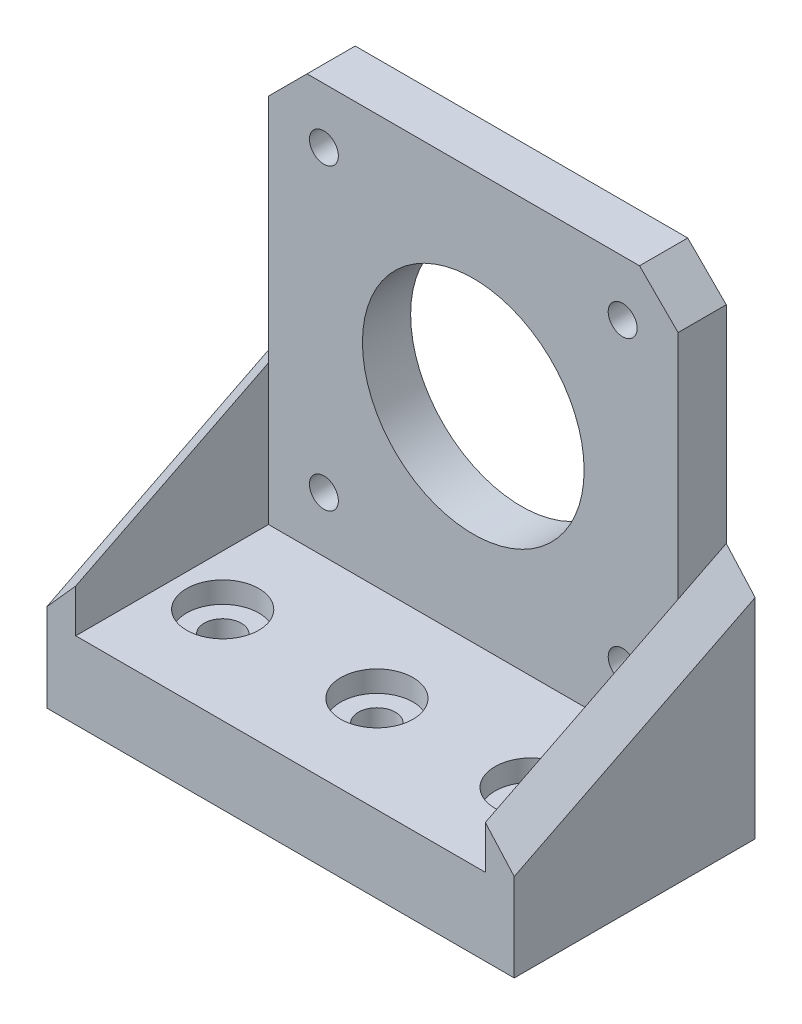
SolidWorks part; units mm, degrees
ref_plane "Front Plane" through (0, 0, 0) normal (0, 0, 1) x (1, 0, 0)
ref_plane "Top Plane" through (0, 0, 0) normal (0, 1, 0) x (1, 0, 0)
ref_plane "Right Plane" through (0, 0, 0) normal (1, 0, 0) x (0, 0, -1)
sketch "Sketch1" plane through (0, 0, 0) normal (0, 0, 1) x (1, 0, 0)
  line L0 (0, 0) -> (0, 10.5968) construction
  line L1 (-21.25, -21.25) -> (21.25, -21.25)
  line L2 (-21.25, -21.25) -> (-21.25, 21.25)
  line L3 (-21.25, 21.25) -> (21.25, 21.25)
  line L4 (21.25, -21.25) -> (21.25, 21.25)
  line L5 (-21.25, -21.25) -> (21.25, 21.25) construction
  line L6 (-21.25, 21.25) -> (21.25, -21.25) construction
  line L7 (0, 0) -> (-8.9137, 0) construction
  circle A0 centre (15.5, 15.5) radius 1.5
  circle A1 centre (-15.5, 15.5) radius 1.5
  circle A2 centre (15.5, -15.5) radius 1.5
  circle A3 centre (-15.5, -15.5) radius 1.5
  circle A4 centre (0, 0) radius 11.5
  point P0 (0, 0)
  dimension "D5" = 3
  dimension "D6" = 23
  dimension "D1" = 42.5
  dimension "D2" = 42.5
  dimension "D3" = 15.5
  dimension "D4" = 15.5
extrude "Boss-Extrude1" add sketch "Sketch1" along normal blind 5
chamfer "Chamfer1" distance 4 angle 45 2 edges at (-21.25, 21.25, 2.5) (21.25, 21.25, 2.5)
sketch "Sketch2" plane through (0, -21.25, 0) normal (0, -1, 0) x (1, 0, 0)
  line L0 (-21.25, 5) -> (21.25, 5) construction
  line L1 (-21.25, 0) -> (21.25, 0)
  line L2 (-21.25, 0) -> (-21.25, 25)
  line L3 (-21.25, 25) -> (21.25, 25)
  line L4 (21.25, 0) -> (21.25, 25)
  dimension "D1" = 20
extrude "Boss-Extrude2" add sketch "Sketch2" along normal blind 8
sketch "Sketch3" plane through (21.25, 0, 0) normal (1, 0, 0) x (0, 0, -1)
  line L0 (-25, -21.25) -> (0, -8.6817)
  line L1 (0, -29.25) -> (0, 17.25) construction
  line L2 (0, -8.6817) -> (0, -29.25)
  line L3 (0, -29.25) -> (-25, -29.25)
  line L4 (-25, -29.25) -> (-25, -21.25)
extrude "Boss-Extrude3" add sketch "Sketch3" along normal blind 3
mirror "Mirror3" about plane through (0, 0, 0) normal (1, 0, 0) of "Boss-Extrude3"
chamfer "Chamfer2" distance 4 angle 45 2 edges at (-21.25, -9.9385, 2.5) (21.25, -9.9385, 2.5)
sketch "Sketch4" plane through (0, -21.25, 0) normal (0, 1, 0) x (1, 0, 0)
  line L0 (0, -5) -> (0, -25) construction
  line L1 (17.25, -5) -> (-17.25, -5) construction
  line L2 (21.25, -25) -> (-21.25, -25) construction
  circle A0 centre (0, -15) radius 3.75
  circle A1 centre (16, -15) radius 3.75
  circle A2 centre (-16, -15) radius 3.75
  dimension "D1" = 2
  dimension "D3" = 7.5
  dimension "D2" = 2
extrude "Cut-Extrude1" cut sketch "Sketch4" against normal blind 2.2
sketch "Sketch5" plane through (0, -23.45, 0) normal (0, 1, 0) x (1, 0, 0)
  circle A0 centre (0, -15) radius 1.925
  circle A1 centre (16, -15) radius 1.925
  circle A2 centre (-16, -15) radius 1.925
  dimension "D1" = 3.85
  dimension "D2" = 2
  dimension "D3" = 2
extrude "Cut-Extrude2" cut sketch "Sketch5" against normal through all
equation "\"D2@Sketch1\"=\"D1@Sketch1\""
